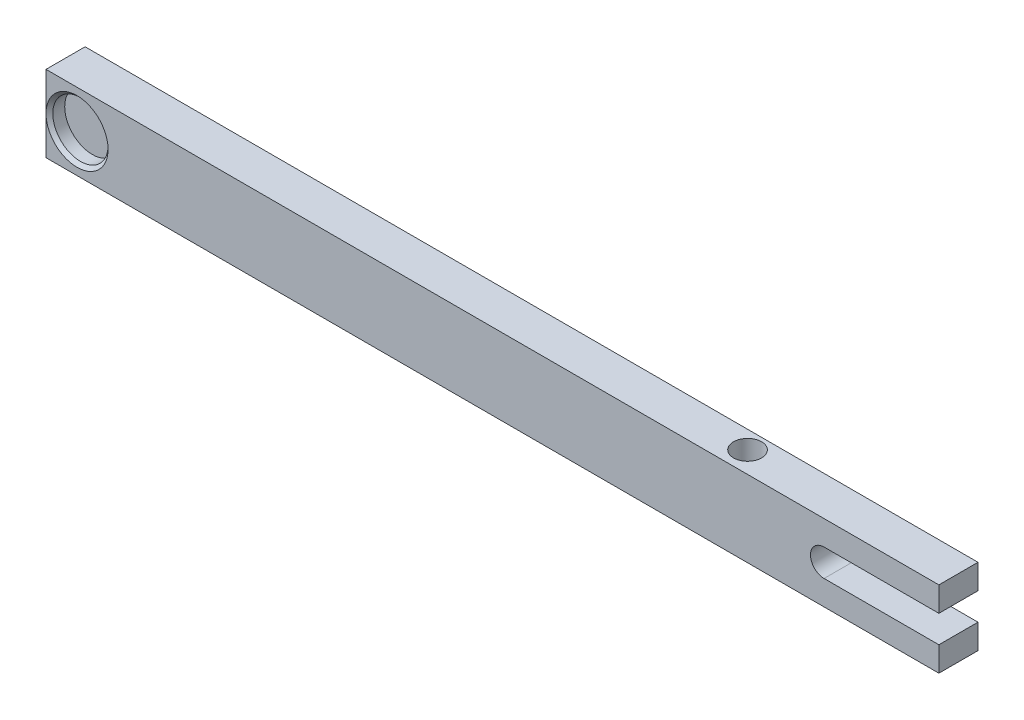
SolidWorks part; units mm, degrees
ref_plane "Front" through (0, 0, 0) normal (0, 0, 1) x (1, 0, 0)
ref_plane "Top" through (0, 0, 0) normal (0, 1, 0) x (1, 0, 0)
ref_plane "Right" through (0, 0, 0) normal (1, 0, 0) x (0, 0, -1)
sketch "Sketch1" plane through (0, 0, 0) normal (0, 0, 1) x (1, 0, 0)
  line L1 (52.5, -4.5) -> (-52.5, -4.5)
  line L2 (52.5, -4.5) -> (52.5, 4.5)
  line L3 (52.5, 4.5) -> (-52.5, 4.5)
  line L4 (-52.5, -4.5) -> (-52.5, 4.5)
  line L5 (52.5, -4.5) -> (-52.5, 4.5) construction
  line L6 (52.5, 4.5) -> (-52.5, -4.5) construction
  point P0 (0, 0)
  dimension "D1" = 9
  dimension "D2" = 105
extrude "Boss-Extrude1" add sketch "Sketch1" along normal blind 5
sketch "Sketch2" plane through (0, 4.5, 0) normal (0, 1, 0) x (1, 0, 0)
  line L0 (52.5, -5) -> (52.5, 0) construction
  line L2 (52.5, 0) -> (-52.5, 0) construction
  circle A0 centre (27.5, -2.5) radius 1.65
  dimension "D3" = 3.3
  dimension "D2" = 25
  dimension "D1" = 2.5
sketch "Sketch4" plane through (0, 0, 5) normal (0, 0, 1) x (1, 0, 0)
  line L0 (39, 0) -> (45, 0) construction
  line L1 (39, 1.6) -> (45, 1.6)
  line L2 (39, -1.6) -> (45, -1.6)
  arc A0 (39, 1.6) -> (39, -1.6) centre (39, 0) ccw
  arc A1 (45, -1.6) -> (45, 1.6) centre (45, 0) ccw
  point P2 (42, 0)
  dimension "D1" = 1.6
  dimension "D2" = 42
  dimension "D3" = 6
extrude "Cut-Extrude1" cut sketch "Sketch4" against normal blind 5
sketch "Sketch8" plane through (0, 0, 5) normal (0, 0, 1) x (1, 0, 0)
  line L0 (45, 1.6) -> (39, 1.6) construction
  line L1 (44.5, 1.6) -> (52.5, 1.6)
  line L2 (44.5, 1.6) -> (44.5, -1.6)
  line L3 (44.5, -1.6) -> (52.5, -1.6)
  line L4 (52.5, 1.6) -> (52.5, -1.6)
  line L5 (52.5, -4.5) -> (52.5, 4.5) construction
  line L6 (39, -1.6) -> (45, -1.6) construction
  dimension "D1" = 8
extrude "Cut-Extrude4" cut sketch "Sketch8" against normal blind 10
ref_plane "Plane1" through (-48.5, 0, 0) normal (-1, 0, 0) x (0, 0, 1)
sketch "Sketch7" plane through (0, 0, 5) normal (0, 0, -1) x (-1, 0, 0)
  line L1 (52.5, 4.5) -> (52.5, -4.5) construction
  circle A0 centre (48.85, 0) radius 3.25
  dimension "D1" = 6.5
  dimension "D2" = 3.65
extrude "Cut-Extrude2" cut sketch "Sketch7" along normal blind 1.8
chamfer "Chamfer1" distance 0.4 angle 45 1 edges at (-52.1, 0, 5)
chamfer "Chamfer2" distance 0.4 angle 45 8 edges at (52.5, 3.05, 0) (52.5, -3.05, 0) (0, 4.5, 0) (-52.5, 0, 0) (0, -4.5, 0) (45.75, -1.6, 0) (37.4, 0, 0) (45.75, 1.6, 0)
extrude "Cut-Extrude3" cut sketch "Sketch2" against normal blind 10
